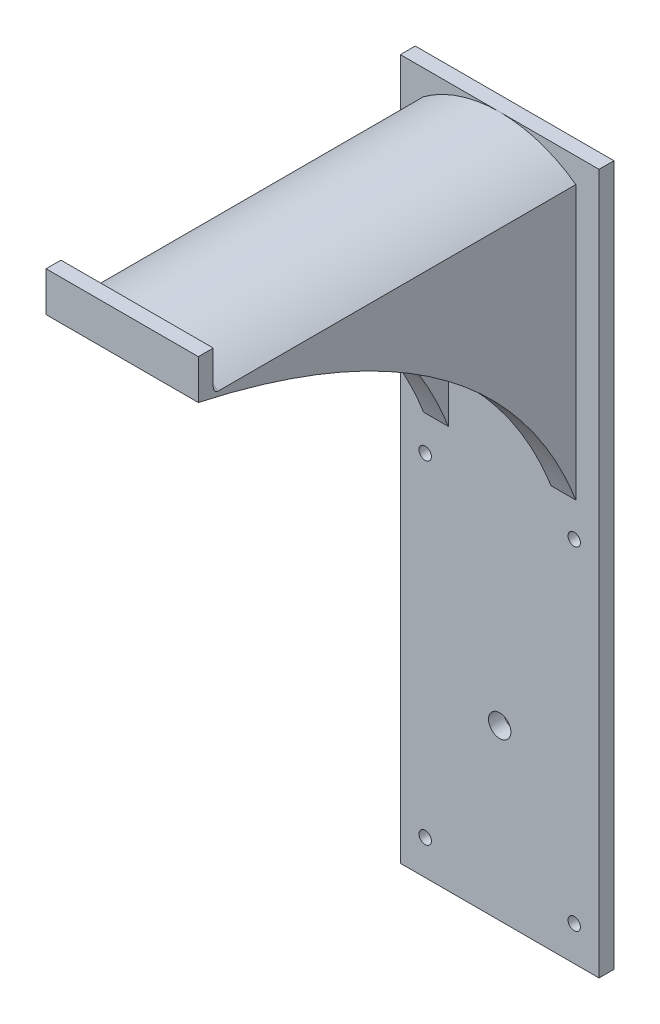
SolidWorks part; units mm, degrees
ref_plane "Piano frontale" through (0, 0, 0) normal (0, 0, 1) x (1, 0, 0)
ref_plane "Piano superiore" through (0, 0, 0) normal (0, 1, 0) x (1, 0, 0)
ref_plane "Piano destro" through (0, 0, 0) normal (1, 0, 0) x (0, 0, -1)
sketch "Schizzo1" plane through (0, 0, 0) normal (0, 0, 1) x (1, 0, 0)
  line L0 (-15.3297, 65.5) -> (15.3297, 65.5)
  line L1 (20, -70.5) -> (-20, -70.5)
  line L3 (20, 70.5) -> (-20, 70.5)
  line L5 (20, -13.4286) -> (-20, 13.4286) construction
  line L6 (20, 13.4286) -> (-20, -13.4286) construction
  line L8 (0, 65.5) -> (0, -2.5) construction
  line L9 (0, -2.5) -> (0, -70.5) construction
  line L10 (-20, 70.5) -> (20, 70.5)
  line L11 (-20, 70.5) -> (-20, -70.5)
  line L12 (-20, -70.5) -> (20, -70.5)
  line L13 (20, 70.5) -> (20, -70.5)
  line L14 (-20, 70.5) -> (20, -70.5) construction
  line L15 (-20, -70.5) -> (20, 70.5) construction
  arc A0 (15.3297, 65.5) -> (-15.3297, 65.5) centre (0, 44.5) ccw
  circle A1 centre (0, 44.5) radius 2.25
  circle A2 centre (0, -36.5) radius 2.25
  point P0 (0, 0)
  point P8 (0, 70.5)
  point P16 (0, 0)
  dimension "D3" = 52
  dimension "D5" = 4.5
  dimension "D1" = 141
  dimension "D4" = 5
  dimension "D6" = 40
extrude "Estrusione-Estrusione4" add sketch "Schizzo1" along normal blind 3 contours A0 L0 L10 L11 L1 L13 L3 A2 A1 | L0 A0 region at (0, 67.5175, 0) region at (0, -1.3031, 0)
sketch "Schizzo2" plane through (0, 0, 3) normal (0, 0, 1) x (1, 0, 0)
  line L0 (20, 70.5) -> (-20, 70.5) construction
  line L1 (20, 70.5) -> (-20, 70.5)
  line L2 (-15.3297, 65.5) -> (15.3297, 65.5)
  arc A0 (15.3297, 65.5) -> (-15.3297, 65.5) centre (0, 44.5) ccw
  point P4 (0, 70.5)
  dimension "D1" = 52
  dimension "D2" = 5
extrude "Estrusione-Estrusione5" add sketch "Schizzo2" along normal blind 73 contours L2 A0 region at (0, 67.5175, 3)
sketch "Schizzo3" plane through (0, 0, 76) normal (0, 0, 1) x (1, 0, 0)
  line L1 (15.3297, 65.5) -> (-15.3297, 65.5)
  line L2 (15.3297, 65.5) -> (15.3297, 73.5)
  line L3 (15.3297, 73.5) -> (-15.3297, 73.5)
  line L4 (-15.3297, 65.5) -> (-15.3297, 73.5)
  dimension "D1" = 8
extrude "Estrusione-Estrusione6" add sketch "Schizzo3" along normal blind 3
fillet "Raccordo1" radius 1 1 edges at (0, 70.5, 76)
sketch "Schizzo4" plane through (0, 0, 3) normal (0, 0, 1) x (1, 0, 0)
  line L1 (-15.3297, 65.5) -> (-10.3297, 65.5)
  line L2 (-15.3297, 65.5) -> (-15.3297, 10.5)
  line L3 (-15.3297, 10.5) -> (-10.3297, 10.5)
  line L4 (-10.3297, 65.5) -> (-10.3297, 10.5)
  line L5 (15.3297, 65.5) -> (10.3297, 65.5)
  line L6 (15.3297, 65.5) -> (15.3297, 10.5)
  line L7 (15.3297, 10.5) -> (10.3297, 10.5)
  line L8 (10.3297, 65.5) -> (10.3297, 10.5)
  dimension "D1" = 55
  dimension "D2" = 5
extrude "Estrusione-Estrusione7" add sketch "Schizzo4" along normal up to surface (76 mm away) up to face at (0, 69.5, 79)
sketch "Schizzo5" plane through (15.3297, 0, 0) normal (1, 0, 0) x (0, 0, -1)
  line L0 (-75, 65.5) -> (-79, 65.5)
  line L1 (-79, 10.5) -> (-79, 73.5) construction
  line L2 (-79, 10.5) -> (-3, 10.5) construction
  line L3 (-79, 10.5) -> (-3, 10.5)
  line L4 (-79, 10.5) -> (-79, 73.5)
  spline S0 degree 3 poles (-79, 65.5) (-47.7082, 58.6573) (-15.7201, 43.4536) (-3, 10.5) knots 0 0 0 0 1 1 1 1
  point P6 (-60.9549, 60.5387)
  line M1 (-79, 73.5) -> (-79, 10.5)
  line M2 (-79, 10.5) -> (-3, 10.5)
extrude "Taglio-Estrusione1" cut sketch "Schizzo5" against normal up to surface (30.6594 mm away) contours S0 M2 M1 region at (15.3297, 32.04, 49.1317) up to face at (-15.3297, 52.2029, 55.88)
sketch "Schizzo6" plane through (0, 0, 3) normal (0, 0, 1) x (1, 0, 0)
  line L0 (20, -70.5) -> (-20, -70.5) construction
  line L1 (10, 70.5) -> (-10, 70.5)
  line L2 (10, 70.5) -> (10, -70.5)
  line L3 (10, -70.5) -> (-10, -70.5)
  line L4 (-10, 70.5) -> (-10, -70.5)
  line L5 (10, 70.5) -> (-10, -70.5) construction
  line L6 (10, -70.5) -> (-10, 70.5) construction
  line L7 (-20, -70.5) -> (-10, -70.5) construction
  line L8 (-15, -70.5) -> (-15, 10.5) construction
  line L9 (-15.3297, 10.5) -> (-10.3297, 10.5) construction
  circle A0 centre (-15, -63.5) radius 1.25
  circle A2 centre (-15, 3.5) radius 1.25
  point P0 (0, 0)
  dimension "D2" = 2.5
  dimension "D1" = 20
  dimension "D3" = 7
  dimension "D4" = 7
extrude "Taglio-Estrusione2" cut sketch "Schizzo6" against normal through all contours A2 | A0 region at (-15, -63.5, 3) region at (-15, 3.5, 3)
mirror "Specchia1" about plane through (0, 0, 0) normal (1, 0, 0) of "Taglio-Estrusione2"
